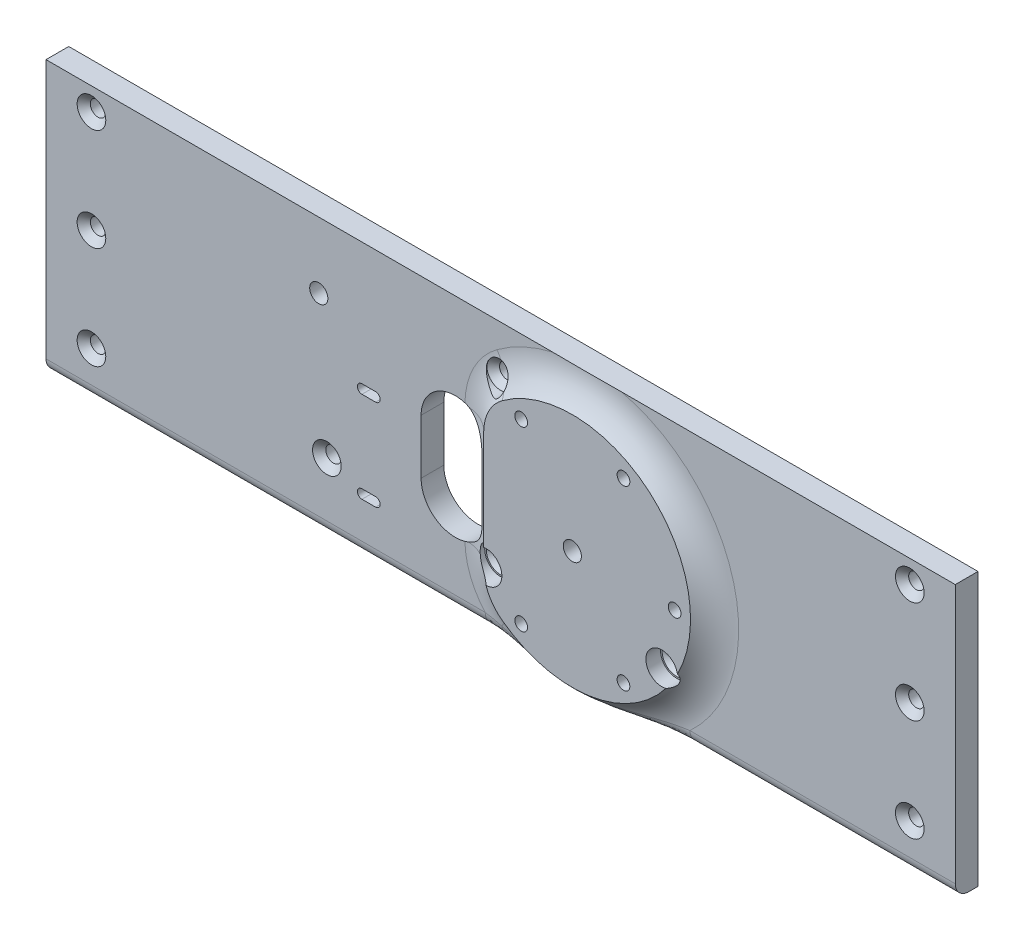
SolidWorks part; units mm, degrees
ref_plane "Front Plane" through (0, 0, 0) normal (0, 0, 1) x (1, 0, 0)
ref_plane "Top Plane" through (0, 0, 0) normal (0, 1, 0) x (1, 0, 0)
ref_plane "Right Plane" through (0, 0, 0) normal (1, 0, 0) x (0, 0, -1)
sketch "Sketch1" plane through (0, 0, 0) normal (0, 0, 1) x (1, 0, 0)
  line L0 (90, 33.5) -> (90, 21.5) construction
  line L1 (0, 0) -> (200, 0)
  line L2 (0, 0) -> (0, 60)
  line L3 (0, 60) -> (200, 60)
  line L4 (200, 0) -> (200, 60)
  line L5 (97.5, 33.5) -> (97.5, 21.5)
  line L6 (82.5, 33.5) -> (82.5, 21.5)
  line L7 (90, 27.5) -> (119, 27.5) construction
  circle A0 centre (119, 27.5) radius 26.5 construction
  circle A2 centre (119, 27.5) radius 2
  circle A3 centre (60, 45.5) radius 2
  arc A4 (97.5, 33.5) -> (82.5, 33.5) centre (90, 33.5) ccw
  arc A5 (82.5, 21.5) -> (97.5, 21.5) centre (90, 21.5) ccw
  arc A6 (142.525, 27.5) -> (140.475, 27.5) centre (141.5, 27.5) ccw construction
  arc A7 (129.225, 8.0144) -> (131.275, 8.0144) centre (130.25, 8.0144) ccw construction
  arc A8 (106.725, 8.0144) -> (108.775, 8.0144) centre (107.75, 8.0144) ccw construction
  arc A9 (106.725, 46.9856) -> (108.775, 46.9856) centre (107.75, 46.9856) ccw construction
  arc A10 (131.275, 46.9856) -> (129.225, 46.9856) centre (130.25, 46.9856) ccw construction
  arc A11 (142.525, 27.5) -> (140.475, 27.5) centre (141.5, 27.5) ccw construction
  arc A12 (129.225, 8.0144) -> (131.275, 8.0144) centre (130.25, 8.0144) ccw construction
  arc A13 (106.725, 8.0144) -> (108.775, 8.0144) centre (107.75, 8.0144) ccw construction
  arc A14 (106.725, 46.9856) -> (108.775, 46.9856) centre (107.75, 46.9856) ccw construction
  arc A15 (131.275, 46.9856) -> (129.225, 46.9856) centre (130.25, 46.9856) ccw construction
  circle A16 centre (130.25, 46.9856) radius 1.4
  circle A17 centre (141.5, 27.5) radius 1.4
  circle A18 centre (130.25, 8.0144) radius 1.4
  circle A19 centre (107.75, 8.0144) radius 1.4
  circle A20 centre (107.75, 46.9856) radius 1.4
  point P8 (90, 27.5)
  dimension "D1" = 4
  dimension "D2" = 4
  dimension "D5" = 53
  dimension "D9" = 1
  dimension "D12" = 5
  dimension "D13" = 2.8
  dimension "D3" = 59
  dimension "D4" = 18
  dimension "D6" = 60
  dimension "D7" = 200
  dimension "D8" = 60
  dimension "D10" = 12
  dimension "D11" = 15
extrude "Boss-Extrude1" add sketch "Sketch1" along normal blind 5
sketch "Sketch3" plane through (0, 0, 5) normal (0, 0, 1) x (1, 0, 0)
  line L0 (99.5, 40.3744) -> (99.5, 14.6256)
  line L1 (97.5, 21.5) -> (97.5, 33.5) construction
  arc A0 (103.5625, 6.5791) -> (103.5625, 48.4209) centre (119, 27.5) ccw
  arc A1 (99.5, 40.3744) -> (103.5625, 48.4209) centre (109.5, 40.3744) cw
  arc A2 (99.5, 14.6256) -> (103.5625, 6.5791) centre (109.5, 14.6256) ccw
  circle A3 centre (119, 27.5) radius 2 construction
  circle A4 centre (107.75, 8.0144) radius 1.4 construction
  circle A5 centre (130.25, 8.0144) radius 1.4 construction
  circle A6 centre (141.5, 27.5) radius 1.4 construction
  circle A7 centre (130.25, 46.9856) radius 1.4 construction
  circle A8 centre (107.75, 46.9856) radius 1.4 construction
  circle A9 centre (119, 27.5) radius 2
  circle A10 centre (107.75, 8.0144) radius 1.4
  circle A11 centre (130.25, 8.0144) radius 1.4
  circle A12 centre (141.5, 27.5) radius 1.4
  circle A13 centre (130.25, 46.9856) radius 1.4
  circle A14 centre (107.75, 46.9856) radius 1.4
  dimension "D1" = 10
  dimension "D3" = 26
  dimension "D2" = 2
extrude "Boss-Extrude2" add sketch "Sketch3" along normal up to surface (3.23 mm away)
fillet "Fillet1" radius 10 4 edges at (100.5732, 10.1187, 5) (99.5, 27.5, 5) (100.5732, 44.8813, 5) (145, 27.5, 5)
sketch "Sketch4" plane through (0, 0, 5) normal (0, 0, 1) x (1, 0, 0)
  line L0 (69.5, 32) -> (72.5, 32) construction
  line L1 (69.5, 33) -> (72.5, 33)
  line L2 (69.5, 31) -> (72.5, 31)
  line L3 (69.5, 12) -> (72.5, 12) construction
  line L4 (69.5, 13) -> (72.5, 13)
  line L5 (69.5, 11) -> (72.5, 11)
  line L6 (0, 0) -> (100.1154, 0) construction
  line L7 (82.5, 33.5) -> (82.5, 21.5) construction
  arc A0 (69.5, 33) -> (69.5, 31) centre (69.5, 32) ccw
  arc A1 (72.5, 31) -> (72.5, 33) centre (72.5, 32) ccw
  arc A2 (69.5, 13) -> (69.5, 11) centre (69.5, 12) ccw
  arc A3 (72.5, 11) -> (72.5, 13) centre (72.5, 12) ccw
  point P2 (71, 32)
  point P7 (71, 12)
  dimension "D1" = 3
  dimension "D2" = 20
  dimension "D3" = 12
  dimension "D4" = 10
  dimension "D5" = 2
extrude "Cut-Extrude1" cut sketch "Sketch4" against normal blind 10
sketch "Sketch8" plane through (0, 0, 5) normal (0, 0, 1) x (1, 0, 0)
  line L0 (10, 55) -> (190, 55) construction
  line L1 (100, 50) -> (100, 60) construction
  line L2 (111.4748, 60) -> (0, 60) construction
  line L3 (61.7843, 15) -> (100, 15) construction
  line L4 (100, 15) -> (100, 50) construction
  line L5 (100, 15) -> (138.6766, 15) construction
  circle A0 centre (190, 10) radius 3 construction
  circle A1 centre (190, 32.5) radius 3 construction
  circle A2 centre (190, 55) radius 3 construction
  circle A3 centre (10, 10) radius 3 construction
  circle A4 centre (10, 32.5) radius 3 construction
  circle A5 centre (10, 55) radius 3 construction
  circle A6 centre (190, 10) radius 3
  circle A7 centre (190, 32.5) radius 3
  circle A8 centre (190, 55) radius 3
  circle A9 centre (10, 10) radius 3
  circle A10 centre (10, 32.5) radius 3
  circle A11 centre (10, 55) radius 3
  circle A12 centre (138.6766, 15) radius 2.1 construction
  circle A13 centre (61.7843, 15) radius 3 construction
  circle A14 centre (138.6766, 15) radius 2.1
  circle A15 centre (61.7843, 15) radius 3
  circle A16 centre (100, 15) radius 3
  circle A17 centre (100, 50) radius 3 construction
  circle A18 centre (100, 50) radius 2.1 construction
  circle A19 centre (100, 50) radius 2.1
hole_wizard "CSK for M3 Flat Head Machine Screw1" positions "3DSketch1" profile "Sketch9" countersink size "M3" standard "ANSI Metric" end condition through all
sketch3d "3DSketch1"
  line L0 (61.7843, 15, 5) -> (100, 15, 5) construction
  line L1 (100, 15, 5) -> (100, 50, 5) construction
  point P0 (10, 55, 5)
  point P3 (10, 32.5, 5)
  point P6 (10, 10, 5)
  point P9 (61.7843, 15, 5)
  point P12 (190, 10, 5)
  point P15 (190, 32.5, 5)
  point P18 (190, 55, 5)
  point P22 (138.6766, 15, 5)
  point P25 (100, 15, 5)
  point P37 (100, 50, 5)
sketch "Sketch9" plane through (10, 55, 5) normal (1, 0, 0) x (0, -1, 0)
  line L0 (0, 0) -> (0, 5)
  line L1 (0, 5) -> (1.7, 5)
  line L2 (1.7, 5) -> (1.7, 1.45)
  line L3 (1.7, 1.45) -> (3.15, 0)
  line L5 (3.15, 0) -> (0, 0)
  line L6 (-1.7, 1.45) -> (-3.15, 0) construction
  line L11 (0, -6.35) -> (0, 107.95) construction
  dimension "Thru Hole Dia." = 3.4
  dimension "Thru Hole Depth" = 5
  dimension "Near C'Sink Dia." = 6.3
  dimension "Near C'Sink Angle" = 90
sketch "Sketch10" plane through (0, 0, 5) normal (0, 0, 1) x (1, 0, 0)
  circle A0 centre (138.6766, 15) radius 3.5
  circle A1 centre (100, 15) radius 3.5
  circle A5 centre (100, 50) radius 3
  dimension "D1" = 7
  dimension "D2" = 6
extrude "Cut-Extrude2" cut sketch "Sketch10" along normal through all
fillet "Fillet2" radius 3 3 edges at (50.0577, 0, 5) (127.8846, 0, 6.0498) (168.9423, 0, 5)
